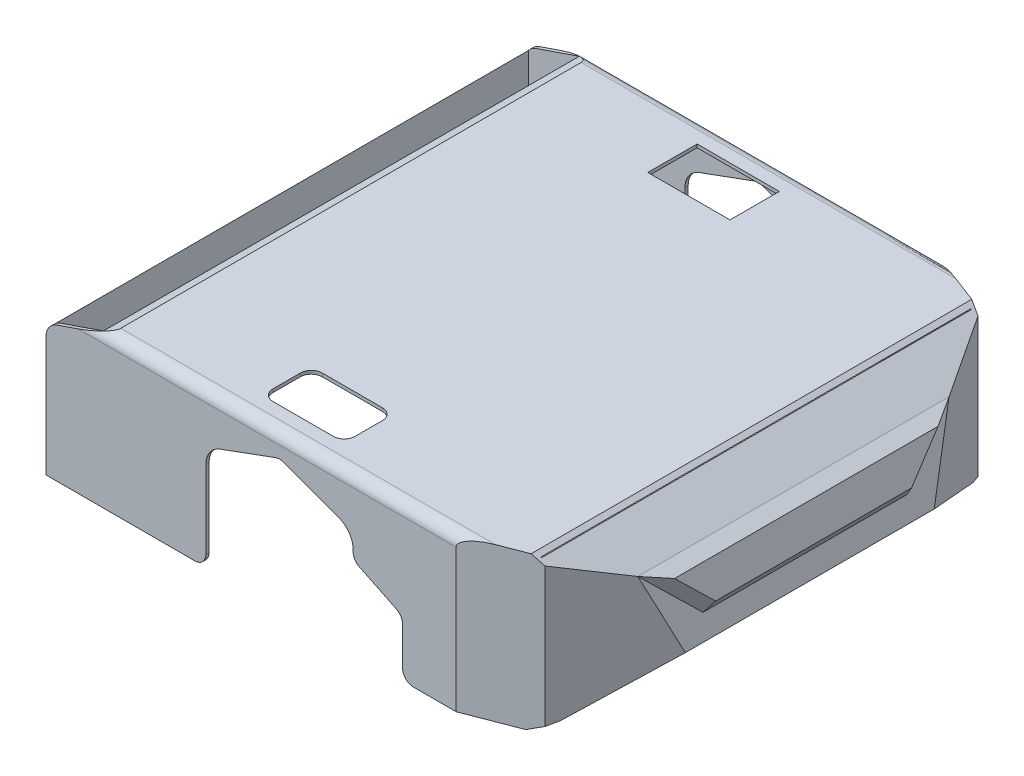
SolidWorks part; units mm, degrees
material "CA"
ref_plane "Front Plane" through (0, 0, 0) normal (0, 0, 1) x (1, 0, 0)
ref_plane "Top Plane" through (0, 0, 0) normal (0, 1, 0) x (1, 0, 0)
ref_plane "Right Plane" through (0, 0, 0) normal (1, 0, 0) x (0, 0, -1)
sketch "Sketch1" plane through (0, 0, 0) normal (0, 0, 1) x (1, 0, 0)
  line L1 (0, 0) -> (480, 0)
  line L2 (0, 0) -> (0, 140)
  line L3 (0, 140) -> (480, 140)
  line L4 (480, 0) -> (480, 140)
  dimension "D1" = 480
  dimension "D2" = 140
extrude "Boss-Extrude1" add sketch "Sketch1" along normal blind 440
sketch "Sketch2" plane through (0, 0, 440) normal (0, 0, 1) x (1, 0, 0)
  line L1 (0, 0) -> (420, 0)
  line L2 (0, 0) -> (0, 120)
  line L3 (0, 120) -> (420, 120)
  line L4 (420, 0) -> (420, 120)
  dimension "D1" = 120
  dimension "D2" = 420
sketch "Sketch3" plane through (0, 0, 440) normal (0, 0, 1) x (1, 0, 0)
  line L0 (0, 120) -> (58.2254, 140)
  line L1 (480, 140) -> (0, 140) construction
  line L2 (58.2254, 140) -> (423.4831, 140)
  line L3 (423.4831, 140) -> (461.8504, 111.6906)
  line L4 (461.8504, 111.6906) -> (480, 30.0603)
  line L5 (480, 0) -> (480, 140) construction
  line L6 (480, 30.0603) -> (420, 0)
  line L7 (0, 120) -> (0, 186.0028)
  line L8 (0, 186.0028) -> (591.5196, 186.0028)
  line L9 (591.5196, 186.0028) -> (591.5196, 0)
  line L10 (591.5196, 0) -> (420, 0)
  line L11 (480, 140) -> (0, 140) construction
extrude "Cut-Extrude2" cut sketch "Sketch3" against normal through all
chamfer "Chamfer1" distance 15 angle 60 1 edges at (480, 30.0603, 220) first distance on face at (470.9252, 70.8754, 220)
sketch "Sketch4" plane through (0, 140, 0) normal (0, 1, 0) x (1, 0, 0)
  line L2 (476.7444, -333.5325) -> (476.7444, -106.4675)
  line L5 (374.147, -440) -> (432.7602, -417.4465)
  line L7 (432.7602, -417.4465) -> (476.7444, -333.5325)
  line L8 (476.7444, -333.5325) -> (476.7444, -220)
  line L9 (476.7444, -440) -> (476.7444, 0) construction
  line L10 (476.7444, -333.5325) -> (476.7444, -220)
  line L11 (476.7444, -220) -> (259.9754, -220) construction
  line L13 (374.147, -440) -> (571.4453, -440)
  line L14 (571.4453, -440) -> (571.4453, 0)
  line L15 (571.4453, 0) -> (374.147, 0)
  line L16 (374.147, 0) -> (432.7602, -22.5535)
  line L17 (432.7602, -22.5535) -> (476.7444, -106.4675)
  line L18 (423.4831, 0) -> (58.2254, 0) construction
  point P14 (476.7444, -220)
extrude "Cut-Extrude3" cut sketch "Sketch4" against normal blind 335 contours L2 L17 L16 L15 L14 L13 L5 L7
fillet "Fillet1" radius 10 2 edges at (216.1862, 140, 0) (216.1862, 140, 440)
fillet "Fillet2" radius 15 1 edges at (0, 120, 220)
sketch "Sketch6" plane through (463.7578, 103.1116, 0) normal (0.9762, 0.217, 0) x (0, 0, -1)
  line L0 (-361.9476, 8.7884) -> (-313.0975, -39.8352)
  line L1 (-313.0975, -39.8352) -> (-126.9025, -39.8352)
  line L2 (-361.9476, 8.7884) -> (-78.0524, 8.7884)
  line L3 (-333.5325, -59.8352) -> (-106.4675, -59.8352)
  line L4 (-220, -59.8352) -> (-220, -40.6647) construction
  line L5 (-78.0524, 8.7884) -> (-361.9476, 8.7884) construction
  line L6 (-78.0524, 8.7884) -> (-126.9025, -39.8352)
  point P10 (-220, -39.8352)
  point P15 (-220, 8.7884)
  line M9 (-78.0524, 8.7884) -> (-361.9476, 8.7884)
  dimension "D1" = 20
extrude "Boss-Extrude2" add sketch "Sketch6" along direction (-0.9762, -0.217, 0) on the side of the normal blind 10 draft 42 contours L4 L1 L6 M9 | L1 L4 L2 L0 region at (466.7614, 89.6024, 220)
sketch "Sketch7" plane through (0, 0, 0) normal (0, -1, 0) x (1, 0, 0)
  line L1 (428.0503, 416.0444) -> (373.5897, 437)
  line L2 (373.5897, 437) -> (3, 437)
  line L3 (3, 437) -> (3, 3)
  line L4 (3, 3) -> (373.5897, 3)
  line L5 (373.5897, 3) -> (428.0503, 23.9556)
  line L14 (428.0503, 23.9556) -> (428.0503, 416.0444)
extrude "Cut-Extrude4" cut sketch "Sketch7" against normal offset from surface (137 mm away) 3 contours L1 L2 L3 L4 L5 L14 up to face at (293.948, 140, 220)
sketch "Sketch8" plane through (0, 140, 0) normal (0, 1, 0) x (1, 0, 0)
  line L0 (58.2254, -220) -> (508.1789, -220) construction
  line L1 (58.2254, -10) -> (58.2254, -430) construction
  line L2 (213, -58.5371) -> (213, -29.5371) construction
  line L3 (200.5, -44.0371) -> (229.5, -44.0371) construction
  line L5 (229.5, -34.5371) -> (229.5, -53.5371) construction
  line L6 (185.5, -373.4629) -> (240.5, -373.4629)
  line L7 (175.5, -66.5371) -> (250.5, -66.5371)
  line L8 (175.5, -66.5371) -> (175.5, -21.5371)
  line L9 (175.5, -21.5371) -> (250.5, -21.5371)
  line L10 (250.5, -66.5371) -> (250.5, -21.5371)
  line L11 (175.5, -66.5371) -> (250.5, -21.5371) construction
  line L12 (175.5, -21.5371) -> (250.5, -66.5371) construction
  line L13 (175.5, -383.4629) -> (175.5, -408.4629)
  line L14 (185.5, -418.4629) -> (240.5, -418.4629)
  line L15 (250.5, -383.4629) -> (250.5, -408.4629)
  arc A0 (185.5, -373.4629) -> (175.5, -383.4629) centre (185.5, -383.4629) ccw
  arc A1 (240.5, -373.4629) -> (250.5, -383.4629) centre (240.5, -383.4629) cw
  arc A2 (175.5, -408.4629) -> (185.5, -418.4629) centre (185.5, -408.4629) ccw
  arc A3 (240.5, -418.4629) -> (250.5, -408.4629) centre (240.5, -408.4629) ccw
  point P17 (213, -44.0371)
  point P25 (175.5, -373.4629)
  point P28 (250.5, -373.4629)
  point P31 (175.5, -418.4629)
  point P34 (250.5, -418.4629)
  dimension "D3" = 10
  dimension "D1" = 75
  dimension "D2" = 45
extrude "Cut-Extrude5" cut sketch "Sketch8" against normal blind 10
sketch "Sketch9" plane through (0, 0, 440) normal (0, 0, 1) x (1, 0, 0)
  line L0 (213, 48.5752) -> (213, 127) construction
  line L1 (213, 119.686) -> (158.9171, 99.8501)
  line L2 (145.8038, 81.0732) -> (145.8038, 0)
  line L3 (0, 0) -> (374.147, 0) construction
  line L4 (145.8038, 0) -> (280.1962, 0)
  line L5 (280.1962, 81.0732) -> (280.1962, 0)
  line L6 (213, 119.686) -> (267.0829, 99.8501)
  arc A0 (234.5, 42.8143) -> (191.5, 42.8143) centre (213, 5.5752) ccw construction
  arc A1 (158.9171, 99.8501) -> (145.8038, 81.0732) centre (165.8038, 81.0732) ccw
  arc A2 (267.0829, 99.8501) -> (280.1962, 81.0732) centre (260.1962, 81.0732) cw
  point P15 (213, 0)
  dimension "D1" = 20
extrude "Cut-Extrude6" cut sketch "Sketch9" against normal blind 674
sketch "Sketch10" plane through (0, 0, 440) normal (0, 0, 1) x (1, 0, 0)
  line L0 (280.1962, 73.1231) -> (319.6001, 53.8513)
  line L1 (280.1962, 0) -> (280.1962, 81.0732) construction
  line L2 (325.2066, 44.8682) -> (325.2066, 0)
  line L3 (280.1962, 0) -> (374.147, 0) construction
  line L4 (325.2066, 0) -> (280.1962, 0)
  line L5 (280.1962, 0) -> (280.1962, 73.1231)
  arc A0 (319.6001, 53.8513) -> (325.2066, 44.8682) centre (315.2066, 44.8682) cw
  dimension "D1" = 10
extrude "Cut-Extrude7" cut sketch "Sketch10" against normal through all
fillet "Fillet3" radius 10 8 edges at (325.2066, 0, 1.5) (145.8038, 0, 1.5) (280.1962, 73.1231, 1.5) (213, 119.686, 1.5) (325.2066, 0, 438.5) (280.1962, 73.1231, 438.5) (145.8038, 0, 438.5) (213, 119.686, 438.5)
